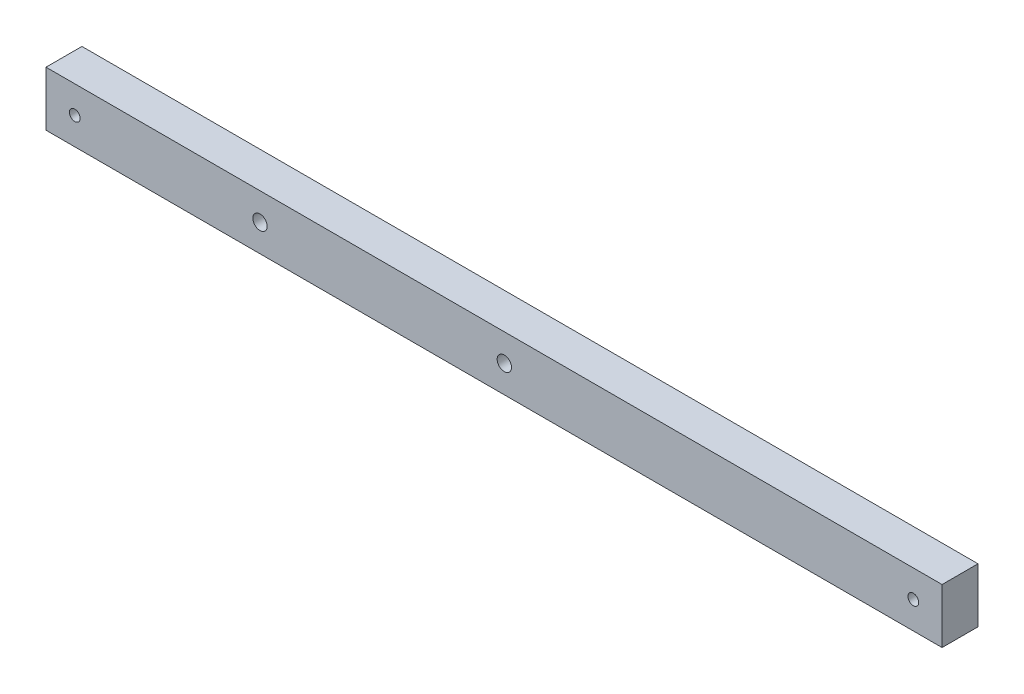
SolidWorks part; units mm, degrees
ref_plane "前视基准面" through (0, 0, 0) normal (0, 0, 1) x (1, 0, 0)
ref_plane "上视基准面" through (0, 0, 0) normal (0, 1, 0) x (1, 0, 0)
ref_plane "右视基准面" through (0, 0, 0) normal (1, 0, 0) x (0, 0, -1)
sketch "草图2" plane through (0, 0, 0) normal (0, 0, 1) x (1, 0, 0)
  line L0 (0, 0) -> (0, -11.1015) construction
  line L1 (-31.175, 1.9) -> (31.175, 1.9)
  line L2 (-31.175, 1.9) -> (-31.175, -1.9)
  line L3 (-31.175, -1.9) -> (31.175, -1.9)
  line L4 (31.175, 1.9) -> (31.175, -1.9)
  line L5 (-31.175, 1.9) -> (31.175, -1.9) construction
  line L6 (-31.175, -1.9) -> (31.175, 1.9) construction
  circle A1 centre (0.7158, 0) radius 0.5
  circle A3 centre (-16.2842, 0) radius 0.5
  circle A5 centre (-16.2842, 0) radius 0.375 construction
  circle A6 centre (0.7158, 0) radius 0.375 construction
  point P0 (0, 0)
  dimension "D3" = 1
  dimension "D5" = 1
  dimension "D1" = 3.8
  dimension "D2" = 62.35
extrude "凸台-拉伸1" add sketch "草图2" along normal blind 2.5
sketch "草图3" plane through (0, 0, 0) normal (0, 0, -1) x (-1, 0, 0)
  line L0 (31.175, 1.9) -> (31.175, -1.9) construction
  line L1 (31.175, -1.9) -> (-31.175, -1.9) construction
  line L2 (-31.175, 1.9) -> (31.175, 1.9) construction
  line L3 (29.175, -1.9) -> (29.175, 1.9) construction
  line L4 (-31.175, 0) -> (-29.175, 0) construction
  line L5 (-31.175, -1.9) -> (-31.175, 1.9) construction
  circle A0 centre (29.175, 0) radius 0.375
  circle A1 centre (-29.175, 0) radius 0.375
  dimension "D1" = 0.75
  dimension "D3" = 0.75
  dimension "D2" = 2
  dimension "D4" = 2
extrude "切除-拉伸1" cut sketch "草图3" against normal up to next
